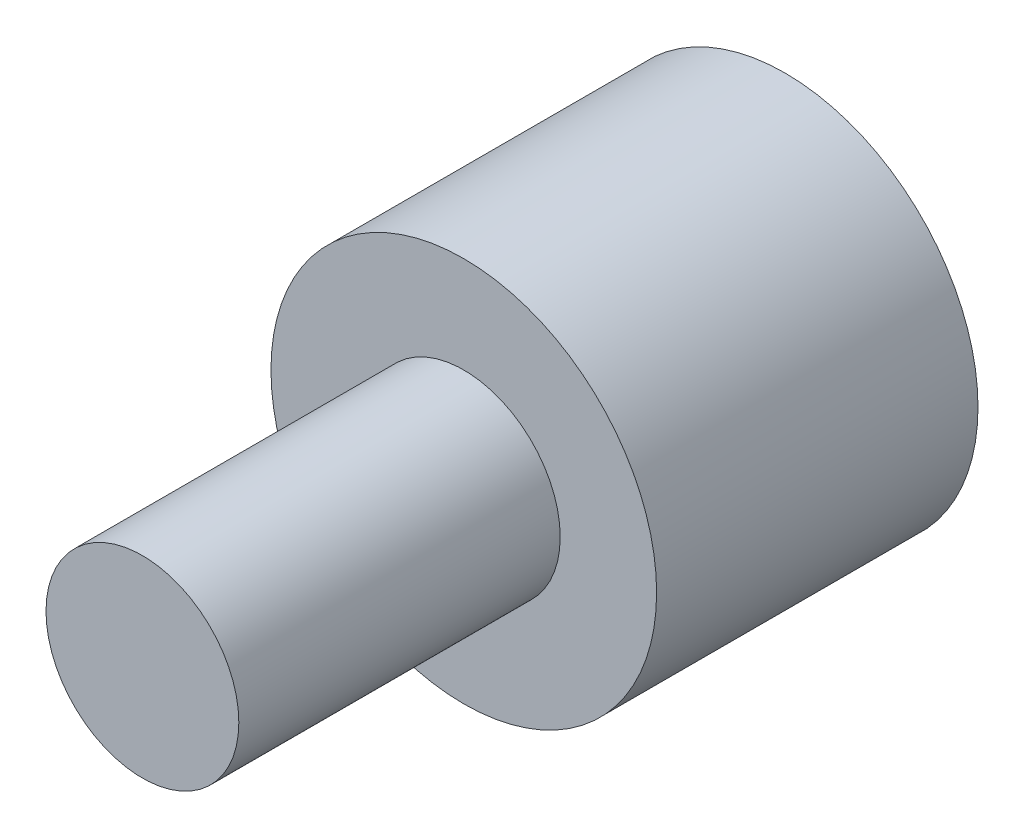
SolidWorks part; units mm, degrees
ref_plane "Front Plane" through (0, 0, 0) normal (0, 0, 1) x (1, 0, 0)
ref_plane "Top Plane" through (0, 0, 0) normal (0, 1, 0) x (1, 0, 0)
ref_plane "Right Plane" through (0, 0, 0) normal (1, 0, 0) x (0, 0, -1)
sketch "Sketch1" plane through (0, 0, 0) normal (0, 0, 1) x (1, 0, 0)
  circle A0 centre (0, 0) radius 12
  circle A2 centre (0, 0) radius 6
  dimension "D1" = 24
  dimension "D2" = 12
extrude "Boss-Extrude1" add sketch "Sketch1" along normal blind 20 contours A0
extrude "Boss-Extrude2" add sketch "Sketch1<3>" along normal blind 40 contours A2
sketch "Sketch1<3>" plane through (0, 0, 0) normal (0, 0, 1) x (1, 0, 0) same geometry as "Sketch1"
sketch "Sketch2" plane through (0, 0, 0) normal (0, 0, -1) x (-1, 0, 0)
  circle A0 centre (0, 0) radius 5
  dimension "D1" = 10
extrude "Cut-Extrude1" cut sketch "Sketch2" against normal blind 12
